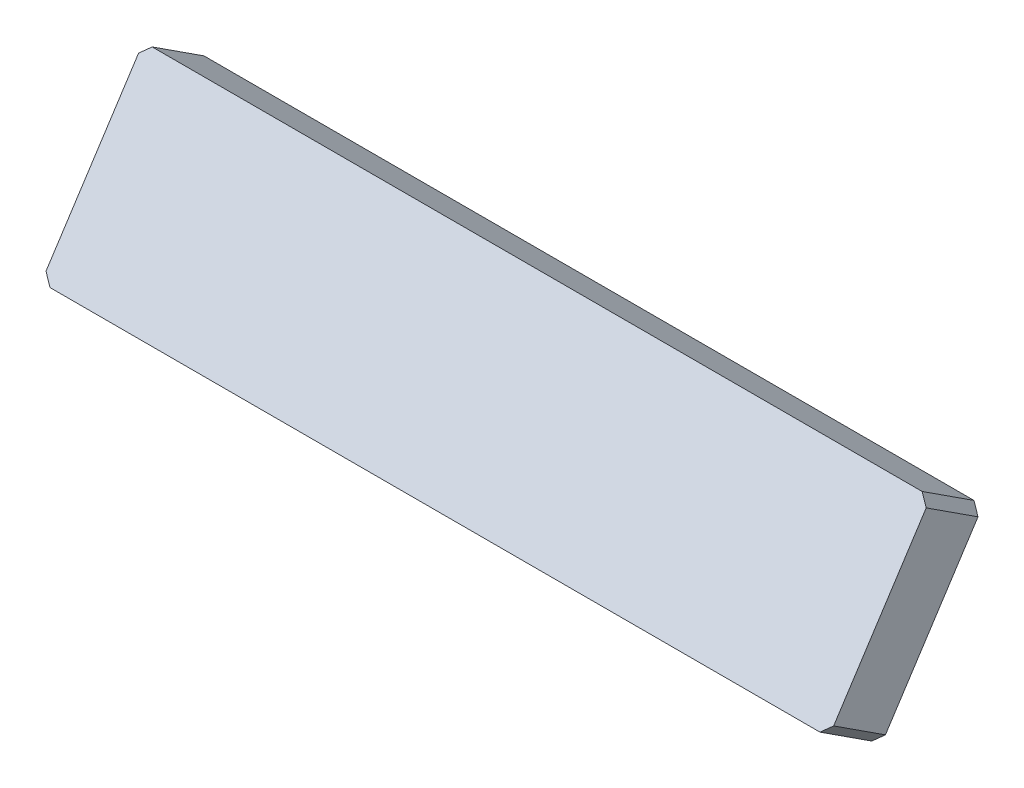
SolidWorks part; units mm, degrees
note: '?' marks a value the reader was unsure of.
ref_plane "Front Plane" through (0, 0, 0) normal (0, 0, 1) x (1, 0, 0)
ref_plane "Top Plane" through (0, 0, 0) normal (0, 1, 0) x (1, 0, 0)
ref_plane "Right Plane" through (0, 0, 0) normal (1, 0, 0) x (0, 0, -1)
sketch "Sketch2" plane through (0, 0, 0) normal (0, 1, 0) x (1, 0, 0)
  line L0 (50.8, 0) -> (-50.8, 0) construction
  circle A0 centre (-50.8, 0) radius 7.6
  circle A1 centre (50.8, 0) radius 7.6
  point P8 (0, 0)
  dimension "D2" = 15.2
  dimension "D1" = 101.6
extrude "Boss-Extrude1" add sketch "Sketch2" along normal blind 19.05
ref_plane "Plane1" through (0, 19.05, 0) normal (0, 1, 0) x (1, 0, 0)
ref_axis "Axis1" through (88.99, 19.05, 0) along (-1, 0, 0)?
ref_plane "Plane2" through (0, 5.6508, 8.7015) normal (0, 0.5446, 0.8387) x (-1, 0, 0)
sketch "Sketch3" plane through (0, 5.6508, 8.7015) normal (0, 0.5446, 0.8387) x (-1, 0, 0)
  line L0 (-50.8, -15.9767) -> (50.8, -15.9767)
  line L2 (-70.85, -32.8517) -> (70.85, -32.8517)
  line L3 (-70.85, -32.8517) -> (-70.85, 0.8983)
  line L4 (-70.85, 0.8983) -> (70.85, 0.8983)
  line L5 (70.85, -32.8517) -> (70.85, 0.8983)
  line L6 (-70.85, -32.8517) -> (70.85, 0.8983) construction
  line L7 (-70.85, 0.8983) -> (70.85, -32.8517) construction
  ellipse E0 centre (50.8, -15.9767) end of major axis (43.2, -15.9767) minor radius 4.1393 construction
  ellipse E1 centre (-50.8, -15.9767) end of major axis (-58.4, -15.9767) minor radius 4.1393 construction
  ellipse E2 centre (50.8, -15.9767) end of major axis (43.2, -15.9767) minor radius 4.1393 construction
  ellipse E3 centre (-50.8, -15.9767) end of major axis (-58.4, -15.9767) minor radius 4.1393 construction
  point P22 (0, -15.9767)
  dimension "D1" = 141.7
  dimension "D2" = 33.75
extrude "Boss-Extrude2" add sketch "Sketch3" along normal blind 12.7
sketch "Sketch8" plane through (0, 19.05, 0) normal (0, 1, 0) x (1, 0, 0)
  line L0 (43.2, 0) -> (58.4, 0) construction
  line L1 (-58.4, 0) -> (-43.2, 0) construction
  line L2 (43.2, 0) -> (58.4, 0)
  line L3 (-58.4, 0) -> (-43.2, 0)
  arc A0 (58.4, 0) -> (43.2, 0) centre (50.8, 0) ccw construction
  arc A1 (-43.2, 0) -> (-58.4, 0) centre (-50.8, 0) ccw construction
  arc A2 (58.4, 0) -> (43.2, 0) centre (50.8, 0) ccw
  arc A3 (-43.2, 0) -> (-58.4, 0) centre (-50.8, 0) ccw
extrude "Boss-Extrude3" add sketch "Sketch8" along normal up to next contours L2 A2 | A3 L3
sketch "Sketch9" plane through (0, 12.5677, 19.3526) normal (0, 0.5446, 0.8387) x (1, 0, 0)
  line L8 (67.875, 29.8767) -> (-67.875, 29.8767)
  line L9 (-67.875, 29.8767) -> (-67.875, 2.0767)
  line L10 (-67.875, 2.0767) -> (67.875, 2.0767)
  line L11 (67.875, 2.0767) -> (67.875, 29.8767)
  line L12 (67.875, 29.8767) -> (-67.875, 29.8767)
  line L13 (-67.875, 29.8767) -> (-67.875, 2.0767)
  line L14 (-67.875, 2.0767) -> (67.875, 2.0767)
  line L15 (67.875, 2.0767) -> (67.875, 29.8767)
  dimension "D1" = 2.975
chamfer "Chamfer2" distance 1.5875 angle 45 12 edges at (-70.85, 19.05, 0) (0, 33.2026, -9.1908) (70.85, 19.05, 0) (0, 4.8974, 9.1908) (0, 11.8143, 19.8419) (-70.85, 8.3559, 14.5163) (-70.85, 25.9669, 10.6511) (70.85, 8.3559, 14.5163) (70.85, 25.9669, 10.6511) (70.85, 36.661, -3.8652) (0, 40.1195, 1.4603) (-70.85, 36.661, -3.8652)
sketch "Sketch10" plane through (0, 5.6508, 8.7015) normal (0, -0.5446, -0.8387) x (-1, 0, 0)
  line L0 (0, 31.2642) -> (0, 0.6892) construction
  line L1 (69.2625, 31.2642) -> (-69.2625, 31.2642) construction
  line L2 (-69.2625, 0.6892) -> (69.2625, 0.6892) construction
  line L3 (-69.2625, 15.9767) -> (69.2625, 15.9767) construction
  line L4 (-69.2625, 31.2642) -> (-69.2625, 0.6892) construction
  line L5 (69.2625, 0.6892) -> (69.2625, 31.2642) construction
  point P6 (0, 15.9767)
